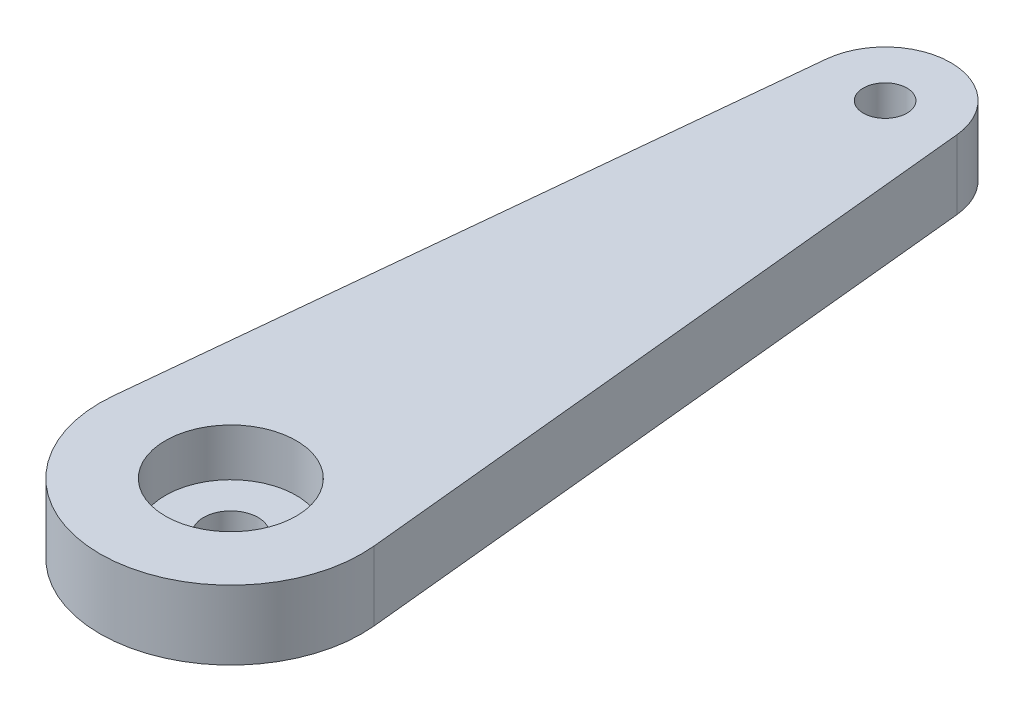
SolidWorks part; units mm, degrees
note: '?' marks a value the reader was unsure of. The reader was unsure of these and kept them because the rebuilt part matched: shared geometry of "Sketch2<4>".
ref_plane "Front Plane" through (0, 0, 0) normal (0, 0, 1) x (1, 0, 0)
ref_plane "Top Plane" through (0, 0, 0) normal (0, 1, 0) x (1, 0, 0)
ref_plane "Right Plane" through (0, 0, 0) normal (1, 0, 0) x (0, 0, -1)
sketch "Sketch2" plane through (0, 0, 0) normal (0, 1, 0) x (1, 0, 0)
  line L2 (0, 0) -> (0, 30) construction
  line L3 (-3, 30.3) -> (-5.9702, 0.597)
  line L4 (3, 30.3) -> (5.9702, 0.597)
  circle A0 centre (0, 0) radius 1.25
  circle A1 centre (0, 30) radius 1
  arc A2 (-3, 30.3) -> (3, 30.3) centre (0, 30) cw
  arc A3 (-5.9702, 0.597) -> (5.9702, 0.597) centre (0, 0) ccw
  circle A4 centre (0, 0) radius 3
  dimension "D1" = 2.5
  dimension "D2" = 2
  dimension "D6" = 6
  dimension "D5" = 3
  dimension "D3" = 30
  dimension "D4" = 3
extrude "Boss-Extrude1" add sketch "Sketch2" along normal blind 3.175
extrude "Boss-Extrude2" add sketch "Sketch2<4>" along normal blind 1
sketch "Sketch2<4>" plane through (0, 0, 0) normal (0, 1, 0) x (1, 0, 0) same geometry as "Sketch2"
sketch "Sketch6" plane through (0, 0, 0) normal (0, 1, 0) x (1, 0, 0)
  line L0 (0, 0) -> (0, 30) construction
ref_axis "Axis1" through (0, 0, 0) along (0, 0, -1)?
extrude "Cut-Extrude1" [suppressed] cut sketch "Sketch7" against normal blind 0.813
sketch "Sketch7" plane through (-69.8875, 0.0003, 82.0487) normal (0, 1, 0) x (0.5, 0, -0.866)
  line L0 (-93.6122, -13.9214) -> (-85.6122, -13.9214) construction
  line L1 (-93.6122, -11.1703) -> (-85.6122, -11.1703)
  line L2 (-93.6122, -16.6726) -> (-85.6122, -16.6726)
  line L3 (-64.1122, -13.9214) -> (-56.1122, -13.9214) construction
  line L4 (-64.1122, -11.1703) -> (-56.1122, -11.1703)
  line L5 (-64.1122, -16.6726) -> (-56.1122, -16.6726)
  line L6 (-92.6994, 27.7536) -> (-84.6994, 27.7536) construction
  line L7 (-92.6994, 30.5047) -> (-84.6994, 30.5047)
  line L8 (-92.6994, 25.0024) -> (-84.6994, 25.0024)
  line L9 (-63.1994, 27.7536) -> (-55.1994, 27.7536) construction
  line L12 (-63.1994, 30.5047) -> (-55.1994, 30.5047)
  line L13 (-63.1994, 25.0024) -> (-55.1994, 25.0024)
  line L14 (18.8632, -13.0451) -> (26.8632, -13.0451) construction
  line L15 (18.8632, -10.294) -> (26.8632, -10.294)
  line L16 (18.8632, -15.7962) -> (26.8632, -15.7962)
  line L17 (49.276, 28.6299) -> (57.276, 28.6299) construction
  line L18 (49.276, 31.381) -> (57.276, 31.381)
  line L19 (49.276, 25.8788) -> (57.276, 25.8788)
  line L20 (48.3632, -13.0451) -> (56.3632, -13.0451) construction
  line L21 (48.3632, -10.294) -> (56.3632, -10.294)
  line L22 (48.3632, -15.7962) -> (56.3632, -15.7962)
  line L23 (27.776, 28.6299) -> (19.776, 28.6299) construction
  line L24 (27.776, 25.8788) -> (19.776, 25.8788)
  line L25 (27.776, 31.381) -> (19.776, 31.381)
  line L27 (-96.8228, -7.9214) -> (-126.8228, -7.9214)
  line L28 (-96.8228, -7.9214) -> (-96.8228, 21.7536)
  line L29 (-96.8228, 21.7536) -> (-126.8228, 21.7536)
  line L30 (-126.8228, -7.9214) -> (-126.8228, 21.7536)
  line L32 (60.4866, -7.0501) -> (90.4866, -7.0501)
  line L33 (60.4866, -7.0501) -> (60.4866, 22.6299)
  line L34 (60.4866, 22.6299) -> (90.4866, 22.6299)
  line L35 (90.4866, -7.0501) -> (90.4866, 22.6299)
  line L37 (-34.9465, 22.1298) -> (-23.1465, 22.1298)
  line L38 (-34.9465, 22.1298) -> (-34.9465, -0.3702)
  line L39 (-34.9465, -0.3702) -> (-23.1465, -0.3702)
  line L40 (-23.1465, 22.1298) -> (-23.1465, -0.3702)
  line L41 (-13.2362, 16.0805) -> (-1.4362, 16.0805)
  line L42 (-13.2362, 16.0805) -> (-13.2362, -6.4195)
  line L43 (-13.2362, -6.4195) -> (-1.4362, -6.4195)
  line L44 (-1.4362, 16.0805) -> (-1.4362, -6.4195)
  circle A0 centre (-29.0465, 24.5298) radius 1
  circle A1 centre (-29.0465, -2.7702) radius 1
  circle A3 centre (-7.3362, 18.4805) radius 1
  circle A4 centre (-7.3362, -8.8195) radius 1
  circle A5 centre (40.7656, -24.5) radius 2.5
  circle A6 centre (40.7656, -14.5) radius 2.5
  arc A8 (-93.6122, -11.1703) -> (-93.6122, -16.6726) centre (-93.6122, -13.9214) ccw
  arc A9 (-85.6122, -16.6726) -> (-85.6122, -11.1703) centre (-85.6122, -13.9214) ccw
  arc A10 (-64.1122, -11.1703) -> (-64.1122, -16.6726) centre (-64.1122, -13.9214) ccw
  arc A11 (-56.1122, -16.6726) -> (-56.1122, -11.1703) centre (-56.1122, -13.9214) ccw
  arc A12 (-92.6994, 30.5047) -> (-92.6994, 25.0024) centre (-92.6994, 27.7536) ccw
  arc A13 (-84.6994, 25.0024) -> (-84.6994, 30.5047) centre (-84.6994, 27.7536) ccw
  arc A16 (49.276, 31.381) -> (49.276, 25.8788) centre (49.276, 28.6299) ccw
  arc A17 (-63.1994, 30.5047) -> (-63.1994, 25.0024) centre (-63.1994, 27.7536) ccw
  arc A18 (-55.1994, 25.0024) -> (-55.1994, 30.5047) centre (-55.1994, 27.7536) ccw
  arc A19 (18.8632, -10.294) -> (18.8632, -15.7962) centre (18.8632, -13.0451) ccw
  arc A20 (26.8632, -15.7962) -> (26.8632, -10.294) centre (26.8632, -13.0451) ccw
  arc A21 (57.276, 25.8788) -> (57.276, 31.381) centre (57.276, 28.6299) ccw
  arc A22 (48.3632, -10.294) -> (48.3632, -15.7962) centre (48.3632, -13.0451) ccw
  arc A23 (56.3632, -15.7962) -> (56.3632, -10.294) centre (56.3632, -13.0451) ccw
  arc A24 (27.776, 25.8788) -> (27.776, 31.381) centre (27.776, 28.6299) ccw
  arc A25 (19.776, 31.381) -> (19.776, 25.8788) centre (19.776, 28.6299) ccw
  point P25 (-89.6122, -13.9214)
  point P30 (-60.1122, -13.9214)
  point P43 (-88.6994, 27.7536)
  point P50 (-59.1994, 27.7536)
  point P56 (22.8632, -13.0451)
  point P67 (53.276, 28.6299)
  point P79 (52.3632, -13.0451)
  point P84 (23.776, 28.6299)
